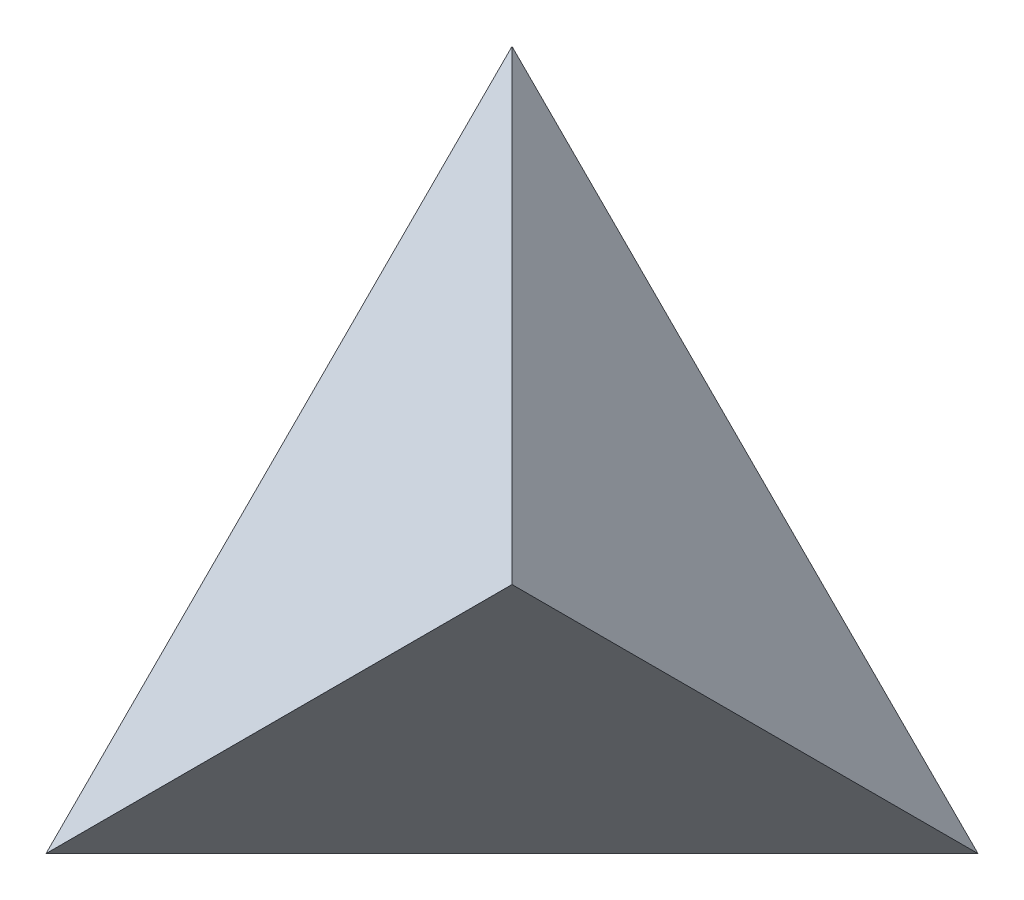
SolidWorks part; units mm, degrees
note: '?' marks a value the reader was unsure of.
ref_plane "Front Plane" through (0, 0, 0) normal (0, 0, 1) x (1, 0, 0)
ref_plane "Top Plane" through (0, 0, 0) normal (0, 1, 0) x (1, 0, 0)
ref_plane "Right Plane" through (0, 0, 0) normal (1, 0, 0) x (0, 0, -1)
sketch "Sketch8" plane through (0, 0, 0) normal (0, 1, 0) x (1, 0, 0)
  line L1 (-8.6602, -8.6602) -> (8.6602, -8.6602) construction
  line L2 (-8.6602, -8.6602) -> (-8.6602, 8.6602) construction
  line L3 (-8.6602, 8.6602) -> (8.6602, 8.6602) construction
  line L4 (8.6602, -8.6602) -> (8.6602, 8.6602) construction
  line L5 (-8.6602, -8.6602) -> (8.6602, 8.6602) construction
  line L6 (-8.6602, 8.6602) -> (8.6602, -8.6602) construction
  circle A0 centre (0, 0) radius 8.6602 construction
  point P0 (0, 0)
  dimension "side" = 24.4948
ref_plane "Plane4" through (0, 0, 8.6602) normal (0, 0, 1) x (1, 0, 0)
sketch "Sketch9" plane through (0, 0, 8.6602) normal (0, 0, 1) x (1, 0, 0)
  line L0 (8.6602, 8.6602) -> (-8.6602, -8.6602) construction
  line L2 (8.6602, 8.6602) -> (8.6602, 0) construction
  line L3 (-8.6602, 0) -> (-8.6602, -8.6602) construction
  line L4 (-8.6602, 0) -> (8.6602, 0) construction
  point P2 (0, 0)
  dimension "side" = 24.4948
ref_plane "Plane5" through (0, 0, -8.6602) normal (0, 0, 1) x (1, 0, 0)
sketch "Sketch10" plane through (0, 0, -8.6602) normal (0, 0, 1) x (1, 0, 0)
  line L0 (8.6602, -8.6602) -> (-8.6602, 8.6602) construction
  line L1 (-8.6602, 0) -> (-8.6602, 8.6602) construction
  line L3 (-8.6602, 0) -> (8.6602, 0) construction
  point P2 (0, 0)
  dimension "side" = 24.4948
ref_plane "Plane7" through (2.8867, 2.8867, -2.8867) normal (-0.5774, -0.5774, 0.5774) x (0.4082, 0.4082, 0.8165)
sketch "Sketch11" plane through (2.8867, 2.8867, -2.8867) normal (-0.5774, -0.5774, 0.5774) x (0.4082, 0.4082, 0.8165)
  line L0 (-7.071, -12.2474) -> (-7.071, 12.2474) construction
  line L1 (-7.071, -12.2474) -> (14.1421, 0)
  line L2 (14.1421, 0) -> (-7.071, 12.2474)
  line L3 (-7.071, 12.2474) -> (-7.071, -12.2474)
  circle A0 centre (0, 0) radius 7.071 construction
surface "Surface-Plane3" sketch "Sketch11"
ref_plane "Plane8" through (-2.8867, -2.8867, -2.8867) normal (0.5774, 0.5774, 0.5774) x (0.4082, 0.4082, -0.8165)
sketch "Sketch12" plane through (-2.8867, -2.8867, -2.8867) normal (0.5774, 0.5774, 0.5774) x (0.4082, 0.4082, -0.8165)
  line L0 (7.071, -12.2474) -> (7.071, 12.2474) construction
  line L1 (-14.1421, 0) -> (7.071, -12.2474)
  line L2 (7.071, -12.2474) -> (7.071, 12.2474)
  line L3 (7.071, 12.2474) -> (-14.1421, 0)
  circle A0 centre (0, 0) radius 7.071 construction
surface "Surface-Plane4" sketch "Sketch12"
ref_axis "Axis1" through (0, 0, 0) along (0, 1, 0)?
pattern_circular "CirPattern2" count 2 over 360 about axis through (0, 0, 0) along (0, 1, 0)
surface "Surface-Knit2"
